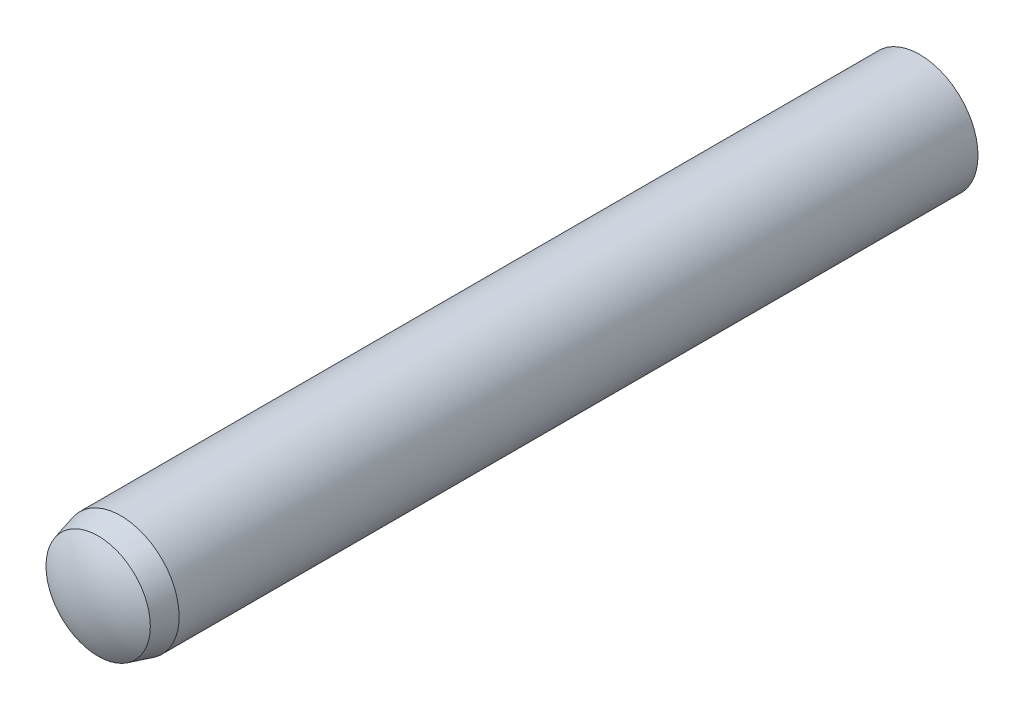
SolidWorks part; units mm, degrees
ref_plane "Front Plane" through (0, 0, 0) normal (0, 0, 1) x (1, 0, 0)
ref_plane "Top Plane" through (0, 0, 0) normal (0, 1, 0) x (1, 0, 0)
ref_plane "Right Plane" through (0, 0, 0) normal (1, 0, 0) x (0, 0, -1)
sketch "Sketch1" plane through (0, 0, 0) normal (0, 0, 1) x (1, 0, 0)
  circle A0 centre (0, 0) radius 1.5
  point P3 (0, 1.5)
  dimension "Diameter" = 3
sketch "Sketch2" plane through (0, 0, 0) normal (1, 0, 0) x (0, 0, -1)
  line L0 (-11, 0) -> (11, 0) construction
  line L1 (-11, 0) -> (-11, 1.5) construction
  line L2 (-11, 1.5) -> (11, 1.5)
  line L3 (11, 1.5) -> (11, 0) construction
  line L4 (-10.61, 1.3432) -> (-10.025, 1.5)
  arc A0 (-11, 0) -> (-10.61, 1.3432) centre (-8.4918, 0) cw
  arc A1 (11, 0) -> (10.55, 1.5) centre (8.275, 0) ccw
  point P2 (0, 0)
  point P11 (-8, 0)
  point P13 (8, 0)
  dimension "D1" = 15
  dimension "D2" = 0.45
  dimension "D3" = 0.975
  dimension "D4" = 0.585
  dimension "D5" = 3
  dimension "D6" = 3
sketch "Sketch3" plane through (0, 0, 0) normal (1, 0, 0) x (0, 0, -1)
  line L0 (-11, 0) -> (11, 0) construction
  line L1 (-10.61, 1.3432) -> (-10.025, 1.5) construction
  line L2 (-11, 0) -> (11, 0)
  line L3 (-10.61, 1.3432) -> (-10.025, 1.5)
  line L4 (-10.025, 1.5) -> (10.55, 1.5)
  arc A0 (11, 0) -> (10.55, 1.5) centre (8.275, 0) ccw construction
  arc A1 (-10.61, 1.3432) -> (-11, 0) centre (-8.4918, 0) ccw construction
  arc A2 (11, 0) -> (10.55, 1.5) centre (8.275, 0) ccw
  arc A3 (-10.61, 1.3432) -> (-11, 0) centre (-8.4918, 0) ccw
revolve "Revolve1" add sketch "Sketch3" angle 360 about L2
equation "\"D2@Sketch2\" = \"Diameter@Sketch1\" * .15"
equation "\"D3@Sketch2\" = \"Diameter@Sketch1\" * .325"
equation "\"D4@Sketch2\" = \"D3@Sketch2\" * .6"
equation "\"D5@Sketch2\"=\"Diameter@Sketch1\""
equation "\"D6@Sketch2\" = \"D5@Sketch2\""
